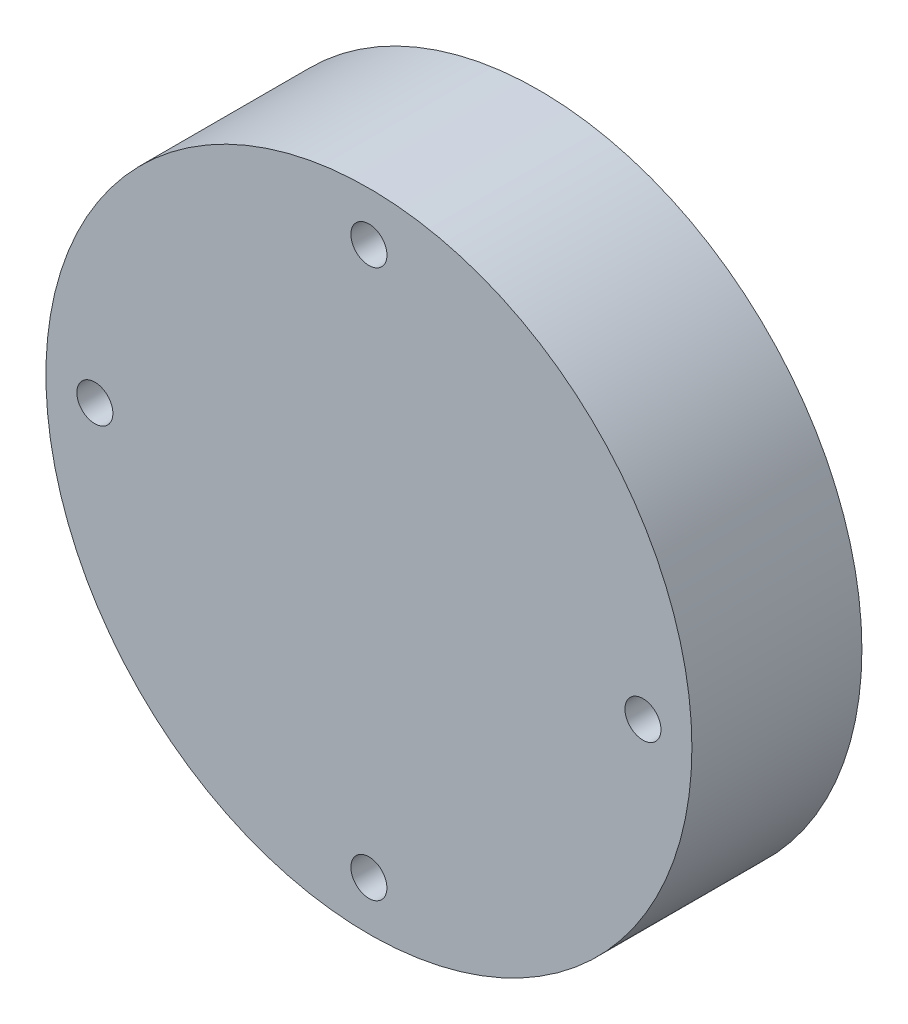
SolidWorks part; units mm, degrees
ref_plane "Plan de face" through (0, 0, 0) normal (0, 0, 1) x (1, 0, 0)
ref_plane "Plan de dessus" through (0, 0, 0) normal (0, 1, 0) x (1, 0, 0)
ref_plane "Plan de droite" through (0, 0, 0) normal (1, 0, 0) x (0, 0, -1)
sketch "Esquisse1" plane through (0, 0, 0) normal (0, 0, 1) x (1, 0, 0)
  circle A0 centre (0, 0) radius 9.5
  dimension "D1" = 19
extrude "Boss.-Extru.1" add sketch "Esquisse1" along normal blind 5
sketch "Esquisse2" plane through (0, 0, 5) normal (0, 0, 1) x (1, 0, 0)
  line L0 (0, 0) -> (0, 2.1842) construction
  circle A0 centre (0, 8.06) radius 0.53
  dimension "D2" = 1.06
  dimension "D1" = 8.06
extrude "Enlèv. mat.-Extru.1" cut sketch "Esquisse2" against normal up to surface (5 mm away) up to face at (9.5, 0, 0)
pattern_circular "Répétition circulaire1" count 4 over 360 about axis through (0, 0, 5) along (0, 0, -1) of "Enlèv. mat.-Extru.1"
